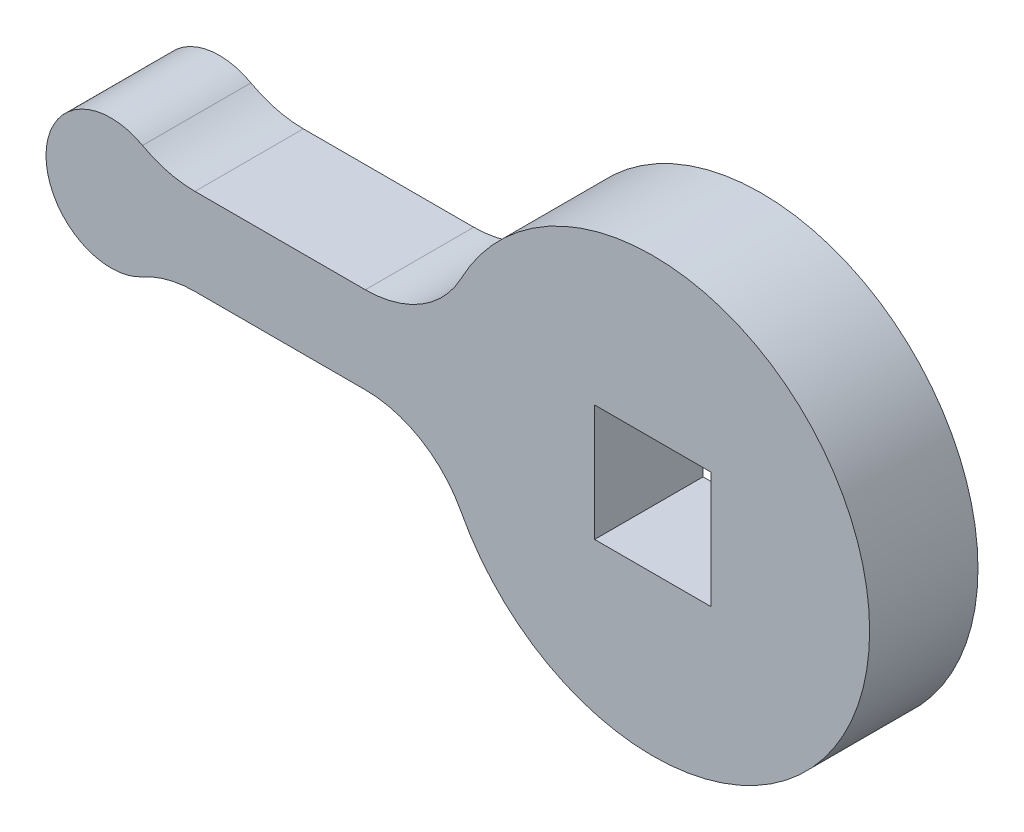
SolidWorks part; units mm, degrees
ref_plane "Front Plane" through (0, 0, 0) normal (0, 0, 1) x (1, 0, 0)
ref_plane "Top Plane" through (0, 0, 0) normal (0, 1, 0) x (1, 0, 0)
ref_plane "Right Plane" through (0, 0, 0) normal (1, 0, 0) x (0, 0, -1)
sketch "Sketch4" plane through (0, 0, 0) normal (0, 0, 1) x (1, 0, 0)
  line L0 (0, 0) -> (0, 10) construction
  line L1 (0, 0) -> (-25, 0) construction
  dimension "D1" = 10
  dimension "D2" = 25
sketch "L" plane through (0, 0, 0) normal (0, 0, 1) x (1, 0, 0)
  line L0 (0, 0) -> (0, -10) construction
  line L1 (0, 0) -> (25, 0) construction
  line L2 (0, 0) -> (0, 10) construction
  line L3 (0, 0) -> (-28.8314, 0) construction
  spline S1 degree 4 poles (2.2591, 8.364) (2.1926, 8.4214) (2.0587, 8.5352) (1.8546, 8.7034) (1.5802, 8.9204) (1.2974, 9.1337) (1.0216, 9.3339) (0.7194, 9.5414) (0.4674, 9.7102) (0.1096, 9.9341) (-0.0654, 10.0403) (-0.3706, 10.2188) (-0.6083, 10.3515) (-0.824, 10.4676) (-1.0114, 10.5652) (-1.1995, 10.6607) (-1.3883, 10.7539) (-1.6102, 10.8597) (-1.9296, 11.0058) (-2.3165, 11.1729) (-2.773, 11.3558) (-3.565, 11.6445) (-4.7747, 12.015) (-6.4247, 12.3753) (-8.5252, 12.5961) (-10.7776, 12.569) (-12.8586, 12.306) (-14.9014, 11.8356) (-16.8881, 11.1667) (-18.8017, 10.3091) (-20.7499, 9.1804) (-22.5734, 7.8599) (-24.0462, 6.5519) (-25.2125, 5.3327) (-26.0266, 4.3648) (-26.5431, 3.6986) (-26.9559, 3.1302) (-27.2753, 2.6678) (-27.5837, 2.1982) (-27.844, 1.7808) (-28.06, 1.4193) (-28.2356, 1.1148) (-28.3737, 0.8687) (-28.5054, 0.628) (-28.6406, 0.3732) (-28.8052, 0.0536) (-28.9094, -0.1553) (-29.1337, -0.6169) (-29.2818, -0.9447) (-29.4691, -1.367) (-29.6265, -1.746) (-29.7889, -2.1515) (-29.9383, -2.5471) (-30.0479, -2.8511) (-30.1178, -3.0528) (-30.1521, -3.1538) knots 0 0 0 0 0 0.008697 0.017393 0.02609 0.034786 0.043356 0.051926 0.060495 0.069065 0.076013 0.082961 0.089909 0.096858 0.100332 0.103806 0.110754 0.117702 0.12465 0.138547 0.152443 0.16634 0.208029 0.263615 0.3192 0.374786 0.430372 0.470684 0.52627 0.581855 0.637441 0.693027 0.748612 0.776405 0.804198 0.818095 0.831991 0.845887 0.859784 0.87368 0.880628 0.887577 0.894525 0.901473 0.908421 0.91537 0.925948 0.936527 0.947106 0.957685 0.968264 0.978842 0.989421 1 1 1 1 1 construction
  spline S2 degree 4 poles (0, 10) (-0.0509, 10.0307) (-0.1543, 10.0923) (-0.3706, 10.2188) (-0.6083, 10.3515) (-0.824, 10.4676) (-1.0114, 10.5652) (-1.1995, 10.6607) (-1.3883, 10.7539) (-1.6102, 10.8597) (-1.9296, 11.0058) (-2.3165, 11.1729) (-2.773, 11.3558) (-3.565, 11.6445) (-4.7747, 12.015) (-6.4247, 12.3753) (-8.5252, 12.5961) (-10.7776, 12.569) (-12.8586, 12.306) (-14.9014, 11.8356) (-16.8881, 11.1667) (-18.8017, 10.3091) (-20.7499, 9.1804) (-22.5734, 7.8599) (-24.0462, 6.5519) (-25.2125, 5.3327) (-26.0266, 4.3648) (-26.5431, 3.6986) (-26.9559, 3.1302) (-27.2753, 2.6678) (-27.5837, 2.1982) (-27.844, 1.7808) (-28.06, 1.4193) (-28.2356, 1.1148) (-28.3737, 0.8687) (-28.5054, 0.628) (-28.6406, 0.3732) (-28.7498, 0.1612) (-28.8047, 0.0531) (-28.8314, 0) knots 0.069065 0.069065 0.069065 0.069065 0.069065 0.076013 0.082961 0.089909 0.096858 0.100332 0.103806 0.110754 0.117702 0.12465 0.138547 0.152443 0.16634 0.208029 0.263615 0.3192 0.374786 0.430372 0.470684 0.52627 0.581855 0.637441 0.693027 0.748612 0.776405 0.804198 0.818095 0.831991 0.845887 0.859784 0.87368 0.880628 0.887577 0.894525 0.901473 0.908421 0.91537 0.91537 0.91537 0.91537 0.91537
  dimension "D1" = 10
  dimension "D2" = 25
sketch "Sketch2" plane through (0, 0, 0) normal (0, 0, 1) x (1, 0, 0)
  line L0 (0, 10) -> (10, 0)
  line L1 (10, 0) -> (-28.8314, 0)
  spline S0 degree 4 poles (1711.3489, -1024.1766) (-44.469, 36.4589) (3.6301, 7.7183) (0.663, 9.6418) (-0.6083, 10.3515) (-0.824, 10.4676) (-1.0114, 10.5652) (-1.1995, 10.6607) (-1.3883, 10.7539) (-1.6102, 10.8597) (-1.9296, 11.0058) (-2.3165, 11.1729) (-2.773, 11.3558) (-3.565, 11.6445) (-4.7747, 12.015) (-6.4247, 12.3753) (-8.5252, 12.5961) (-10.7776, 12.569) (-12.8586, 12.306) (-14.9014, 11.8356) (-16.8881, 11.1667) (-18.8017, 10.3091) (-20.7499, 9.1804) (-22.5734, 7.8599) (-24.0462, 6.5519) (-25.2125, 5.3327) (-26.0266, 4.3648) (-26.5431, 3.6986) (-26.9559, 3.1302) (-27.2753, 2.6678) (-27.5837, 2.1982) (-27.844, 1.7808) (-28.06, 1.4193) (-28.2356, 1.1148) (-28.3737, 0.8687) (-28.5054, 0.628) (-29.2767, -0.8255) (-30.4266, -3.3205) (-7.8225, 41.2196) (-925.9153, -1786.783) knots -0.05179 -0.05179 -0.05179 -0.05179 -0.05179 0.076013 0.082961 0.089909 0.096858 0.100332 0.103806 0.110754 0.117702 0.12465 0.138547 0.152443 0.16634 0.208029 0.263615 0.3192 0.374786 0.430372 0.470684 0.52627 0.581855 0.637441 0.693027 0.748612 0.776405 0.804198 0.818095 0.831991 0.845887 0.859784 0.87368 0.880628 0.887577 0.894525 0.901473 0.908421 1.046125 1.046125 1.046125 1.046125 1.046125 only from (0, 10) to (-28.8314, 0) construction
  spline S1 degree 4 poles (0, 10) (-0.0509, 10.0307) (-0.1543, 10.0923) (-0.3706, 10.2188) (-0.6083, 10.3515) (-0.824, 10.4676) (-1.0114, 10.5652) (-1.1995, 10.6607) (-1.3883, 10.7539) (-1.6102, 10.8597) (-1.9296, 11.0058) (-2.3165, 11.1729) (-2.773, 11.3558) (-3.565, 11.6445) (-4.7747, 12.015) (-6.4247, 12.3753) (-8.5252, 12.5961) (-10.7776, 12.569) (-12.8586, 12.306) (-14.9014, 11.8356) (-16.8881, 11.1667) (-18.8017, 10.3091) (-20.7499, 9.1804) (-22.5734, 7.8599) (-24.0462, 6.5519) (-25.2125, 5.3327) (-26.0266, 4.3648) (-26.5431, 3.6986) (-26.9559, 3.1302) (-27.2753, 2.6678) (-27.5837, 2.1982) (-27.844, 1.7808) (-28.06, 1.4193) (-28.2356, 1.1148) (-28.3737, 0.8687) (-28.5054, 0.628) (-28.6406, 0.3732) (-28.7498, 0.1612) (-28.8047, 0.0531) (-28.8314, 0) knots 0.069065 0.069065 0.069065 0.069065 0.069065 0.076013 0.082961 0.089909 0.096858 0.100332 0.103806 0.110754 0.117702 0.12465 0.138547 0.152443 0.16634 0.208029 0.263615 0.3192 0.374786 0.430372 0.470684 0.52627 0.581855 0.637441 0.693027 0.748612 0.776405 0.804198 0.818095 0.831991 0.845887 0.859784 0.87368 0.880628 0.887577 0.894525 0.901473 0.908421 0.91537 0.91537 0.91537 0.91537 0.91537
  dimension "D1" = 10
extrude "Boss-Extrude1" [suppressed] add sketch "Sketch2" against normal blind 10
mirror "Mirror1" [suppressed] of bodies 101
fillet "Fillet1" [suppressed] radius 5
sketch "Sketch5" plane through (0, 0, 0) normal (0, 0, 1) x (1, 0, 0)
  line L0 (0, 10) -> (0, 0) construction
  line L1 (0, 0) -> (-25, 0)
  line L2 (0, 0) -> (10, 0)
  arc A0 (10, 0) -> (0, 10) centre (0, 0) ccw
  ellipse E0 centre (0, 0) end of major axis (-25, 0) minor radius 10 (0, 10) -> (-25, 0) ccw
extrude "Boss-Extrude5" [suppressed] add sketch "Sketch5" against normal blind 10 contours E0 L1 L2 A0
mirror "Mirror2" [suppressed] of bodies 107 108
sketch "Sketch3" plane through (0, 0, 0) normal (0, 0, 1) x (1, 0, 0)
  line L1 (2.687, -2.687) -> (-2.687, -2.687)
  line L2 (2.687, -2.687) -> (2.687, 2.687)
  line L3 (2.687, 2.687) -> (-2.687, 2.687)
  line L4 (-2.687, -2.687) -> (-2.687, 2.687)
  line L5 (2.687, -2.687) -> (-2.687, 2.687) construction
  line L6 (2.687, 2.687) -> (-2.687, -2.687) construction
  circle A0 centre (0, 0) radius 3.8 construction
  dimension "D1" = 7.6
extrude "Cut-Extrude2" [suppressed] cut sketch "Sketch3" against normal through all contours L3 L4 L1 L2
sketch "Sketch6" plane through (0, 0, 0) normal (0, 0, 1) x (1, 0, 0)
  line L0 (-22.7639, 2) -> (-9.798, 2)
  line L1 (-9.798, -2) -> (-22.7639, -2)
  arc A0 (-9.798, -2) -> (-9.798, 2) centre (0, 0) ccw
  arc A1 (-22.7639, 2) -> (-22.7639, -2) centre (-25, 0) ccw
  point P11 (0, 0)
  point P12 (0, 0)
  point P13 (0, 0)
  point P14 (0, 0)
  dimension "D1" = 6
  dimension "D2" = 4
extrude "Boss-Extrude8" add sketch "Sketch6" along normal blind 5
extrude "Cut-Extrude3" cut sketch "Sketch3<3>" along normal through all contours L3 L4 L1 L2
sketch "Sketch3<3>" plane through (0, 0, 0) normal (0, 0, 1) x (1, 0, 0) same geometry as "Sketch3"
fillet "Fillet4" radius 5 4 edges at (-22.7639, 2, 2.5) (-9.798, -2, 2.5) (-22.7639, -2, 2.5) (-9.798, 2, 2.5)
equation "\"r1\"= 10"
equation "\"r2\"= 25"
equation "\"D1@Sketch4\"=\"r1\""
equation "\"D2@Sketch4\"=\"r2\""
equation "\"shaft\"= 7.6"
equation "\"D1@Sketch3\"=\"shaft\""
equation "\"t\"= 10"
equation "\"D1@Boss-Extrude1\"=\"t\""
equation "\"D1@Boss-Extrude5\"=\"t\""
equation "\"D1@L\" = \"r1\""
equation "\"D2@L\" = \"r2\""
